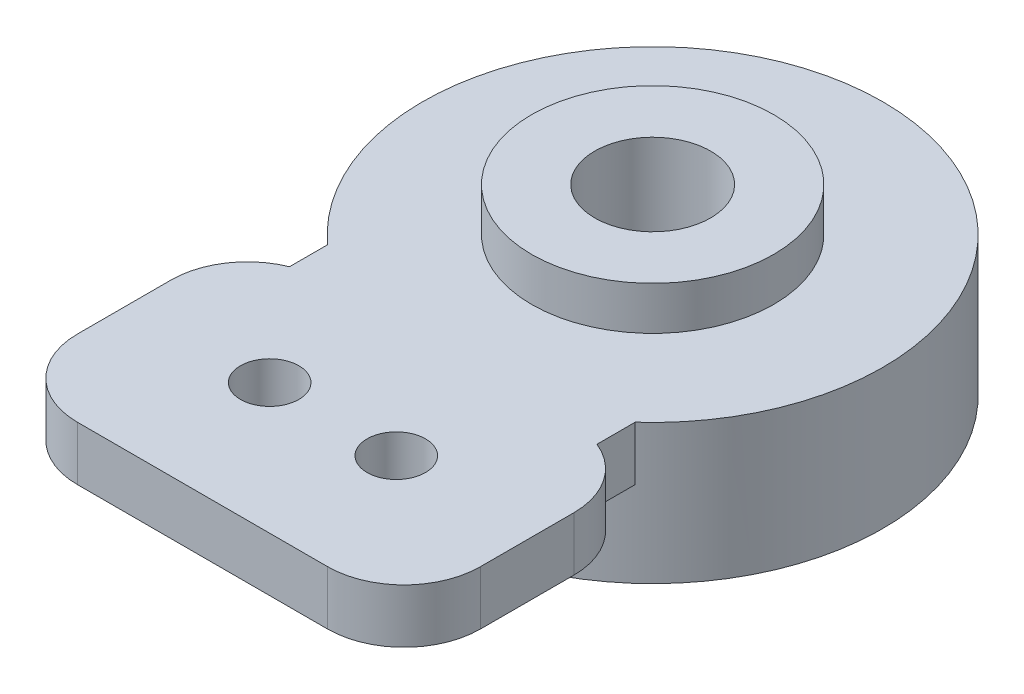
SolidWorks part; units mm, degrees
ref_plane "Front Plane" through (0, 0, 0) normal (0, 0, 1) x (1, 0, 0)
ref_plane "Top Plane" through (0, 0, 0) normal (0, 1, 0) x (1, 0, 0)
ref_plane "Right Plane" through (0, 0, 0) normal (1, 0, 0) x (0, 0, -1)
sketch "Sketch1" plane through (0, 0, 0) normal (0, 1, 0) x (1, 0, 0)
  line L0 (0, 0) -> (0, -17.1224) construction
  line L1 (-6.55, -23.57) -> (6.55, -23.57)
  line L2 (-10.55, -19.57) -> (-10.55, -14.6747)
  line L3 (-6.55, -14.6747) -> (6.55, -19.57) construction
  line L4 (10.55, -19.57) -> (10.55, -14.6747)
  line L5 (-6.55, -19.57) -> (6.55, -14.6747) construction
  line L7 (-25.1268, 12.05) -> (38.8699, 12.05) construction
  line L9 (-8.05, -8.9666) -> (-8.05, -10.9666)
  line L10 (8.05, -8.9666) -> (8.05, -10.9666)
  line L11 (-8.05, -9.9666) -> (8.05, -9.9666) construction
  arc A1 (8.05, -10.9666) -> (10.55, -14.6747) centre (6.55, -14.6747) cw
  arc A2 (6.55, -23.57) -> (10.55, -19.57) centre (6.55, -19.57) ccw
  arc A3 (-6.55, -23.57) -> (-10.55, -19.57) centre (-6.55, -19.57) cw
  arc A4 (-10.55, -14.6747) -> (-8.05, -10.9666) centre (-6.55, -14.6747) cw
  arc A5 (8.05, -8.9666) -> (-8.05, -8.9666) centre (0, 0) ccw
  point P3 (0, -17.1224)
  point P4 (0, -17.1224)
  point P5 (0, -17.1224)
  dimension "D1" = 12.05
  dimension "D5" = 4
  dimension "D2" = 35.62
  dimension "D3" = 21.1
  dimension "D6" = 16.1
  dimension "D7" = 2
extrude "Boss-Extrude1" add sketch "Sketch1" along normal blind 2.83
sketch "Sketch2" plane through (0, 0, 0) normal (0, -1, 0) x (1, 0, 0)
  circle A0 centre (0, 0) radius 12.05
  arc A1 (-8.05, 8.9666) -> (8.05, 8.9666) centre (0, 0) ccw construction
extrude "Boss-Extrude2" add sketch "Sketch2" along normal blind 4.48
sketch "Sketch3" plane through (0, 2.83, 0) normal (0, 1, 0) x (1, 0, 0)
  circle A0 centre (0, 0) radius 6.34
  dimension "D1" = 12.68
extrude "Boss-Extrude3" add sketch "Sketch3" along normal blind 2.27
sketch "Sketch4" plane through (0, 5.1, 0) normal (0, 1, 0) x (1, 0, 0)
  circle A0 centre (0, 0) radius 3.035
  dimension "D1" = 6.07
extrude "Cut-Extrude1" cut sketch "Sketch4" against normal through all
sketch "Sketch5" plane through (0, 2.83, 0) normal (0, 1, 0) x (1, 0, 0)
  line L0 (-6.55, -23.57) -> (6.55, -23.57) construction
  line L4 (-3.315, -18.27) -> (3.315, -18.27) construction
  line L5 (0, 0) -> (0, -23.57) construction
  line L6 (-3.315, -16.74) -> (3.315, -16.74) construction
  circle A0 centre (-3.315, -16.74) radius 1.53
  circle A1 centre (3.315, -16.74) radius 1.53
  point P3 (0, -16.74)
  dimension "D1" = 3.06
  dimension "D2" = 6.63
  dimension "D3" = 5.3
extrude "Cut-Extrude2" cut sketch "Sketch5" against normal through all
